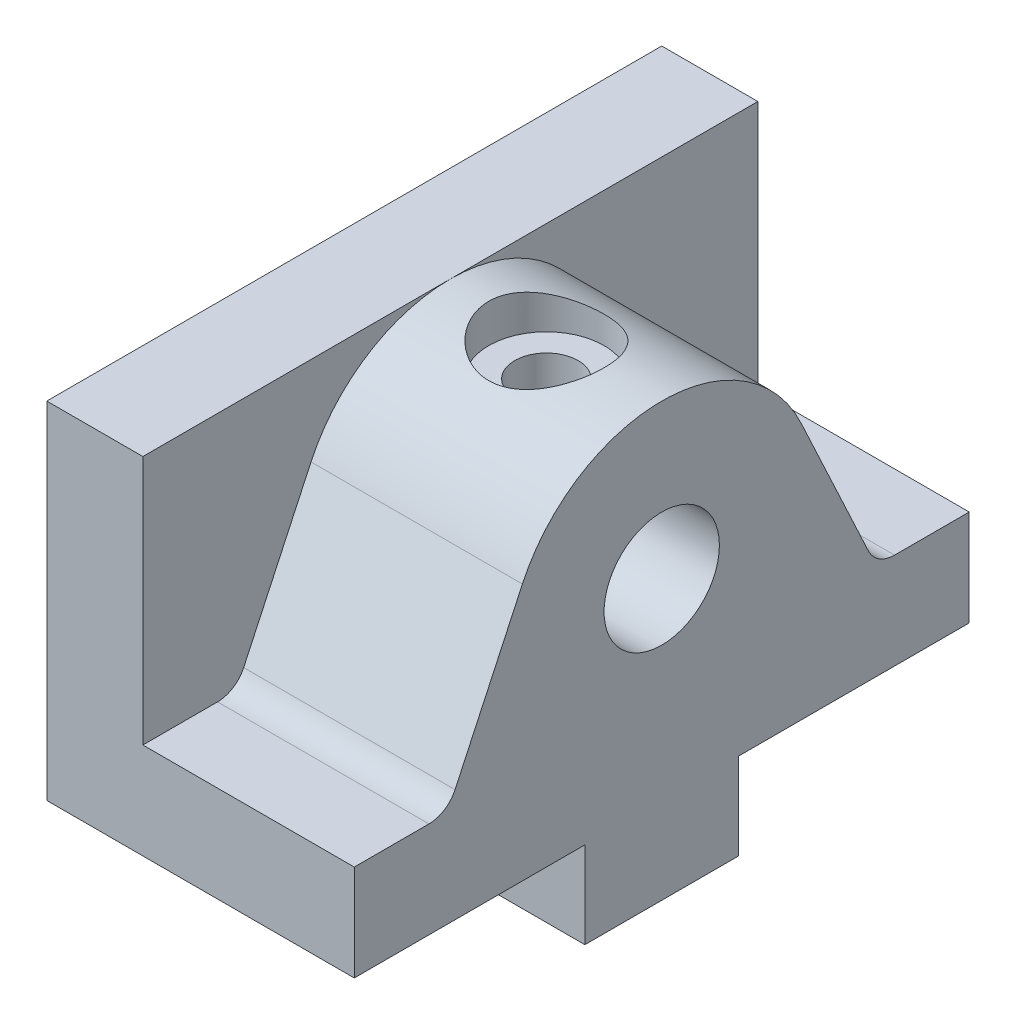
SolidWorks part; units mm, degrees
ref_plane "Front Plane" through (0, 0, 0) normal (0, 0, 1) x (1, 0, 0)
ref_plane "Top Plane" through (0, 0, 0) normal (0, 1, 0) x (1, 0, 0)
ref_plane "Right Plane" through (0, 0, 0) normal (1, 0, 0) x (0, 0, -1)
sketch "Sketch1" plane through (0, 0, 0) normal (1, 0, 0) x (0, 0, -1)
  line L0 (0, 0) -> (0, 27213.6811) construction
  line L1 (0, 0) -> (27213.6811, 0) construction
  line L2 (-32, -8) -> (32, -8)
  line L3 (-32, -18) -> (32, -18)
  line L4 (-32, -18) -> (-32, 18)
  line L5 (-32, 18) -> (32, 18)
  line L6 (32, -18) -> (32, 18)
  line L7 (-32, -18) -> (32, 18) construction
  line L8 (-32, 18) -> (32, -18) construction
  line L9 (-8, -18) -> (8, -18)
  line L10 (-8, -18) -> (-8, -27)
  line L11 (-8, -27) -> (8, -27)
  line L12 (8, -18) -> (8, -27)
  line L13 (-22.3171, -8) -> (-14.5009, 8.7619)
  line L14 (14.5009, 8.7619) -> (22.3171, -8)
  arc A0 (-14.5009, 8.7619) -> (14.5009, 8.7619) centre (0, 2) cw
  circle A1 centre (0, 2) radius 6
  point P5 (0, 0)
  dimension "D6" = 50
  dimension "D7" = 16
  dimension "D8" = 12
  dimension "D1" = 64
  dimension "D2" = 36
  dimension "D3" = 16
  dimension "D4" = 9
  dimension "D5" = 10
extrude "Boss-Extrude1" add sketch "Sketch1" along normal blind 32 contours L3 L6 L2 L4 | L12 L3 L10 L11 | A0 L13 L2 L14 A1 | A1 region at (0, -13, 0) region at (0, 0.1626, 17.9409) region at (0, -22.5, 0) region at (0, 2, 0)
extrude "Boss-Extrude2" add sketch "Sketch1<3>" along normal blind 10 contours L13 A0 L5 L4 L2 | L5 A0 L14 L2 L6 region at (0, 7.0608, 23.1196) region at (0, 7.0608, -23.1196)
sketch "Sketch1<3>" plane through (0, 0, 0) normal (1, 0, 0) x (0, 0, -1) same geometry as "Sketch1"
extrude "Cut-Extrude1" cut sketch "Sketch1<4>" against normal blind 24 from offset 32 contours A1 region at (0, 2, 0)
sketch "Sketch1<4>" plane through (0, 0, 0) normal (1, 0, 0) x (0, 0, -1) same geometry as "Sketch1"
fillet "Fillet1" radius 3 2 edges at (21, -8, -22.3171) (21, -8, 22.3171)
hole_wizard "CBORE for M6 Hex Head Bolt1" positions "Sketch3" profile "Sketch5" counterbore size "M6" standard "ANSI Metric" end condition up to next
sketch "Sketch3" plane through (0, 18, 0) normal (0, 1, 0) x (1, 0, 0)
  line L0 (0, -32) -> (0, 32) construction
  point P0 (20, 0)
  dimension "D1" = 20
sketch "Sketch5" plane through (20, 18, 0) normal (1, 0, 0) x (0, 0, 1)
  line L0 (0, 0) -> (0, 10)
  line L1 (0, 10) -> (3.3, 10)
  line L3 (3.3, 10) -> (3.3, 4)
  line L4 (3.3, 4) -> (6, 4)
  line L5 (6, 4) -> (6, 0)
  line L7 (6, 0) -> (0, 0)
  line L11 (0, -6.35) -> (0, 107.95) construction
  dimension "Thru Hole Dia." = 6.6
  dimension "Thru Hole Depth" = 10
  dimension "C'Bore Dia." = 12
  dimension "C'Bore Depth" = 4
hole_wizard "M6x1.0 Tapped Hole1" positions "Sketch6" profile "Sketch8" tap size "M6x1.0" standard "ANSI Metric"
sketch "Sketch6" plane through (0, -27, 0) normal (0, -1, 0) x (-1, 0, 0)
  line L1 (-32, -8) -> (-32, 8) construction
  point P0 (-24, 0)
  point P2 (-8, 0)
  dimension "D1" = 16
  dimension "D2" = 8
sketch "Sketch8" plane through (24, -27, 0) normal (1, 0, 0) x (0, 0, -1)
  line L0 (0, 0) -> (0, 17.5022)
  line L1 (0, 17.5022) -> (2.5, 16)
  line L2 (2.5, 16) -> (2.5, 0)
  line L5 (2.5, 0) -> (0, 0)
  line L10 (0, 17.5022) -> (-2.5, 16) construction
  line L11 (0, -6.35) -> (0, 107.95) construction
  dimension "Tap Drill Dia." = 5
  dimension "Tap Drill Depth" = 16
  dimension "Drill Angle" = 118
sketch "Sketch10" plane through (0, -27, 0) normal (0, -1, 0) x (1, 0, 0)
  point P0 (0, 0)
